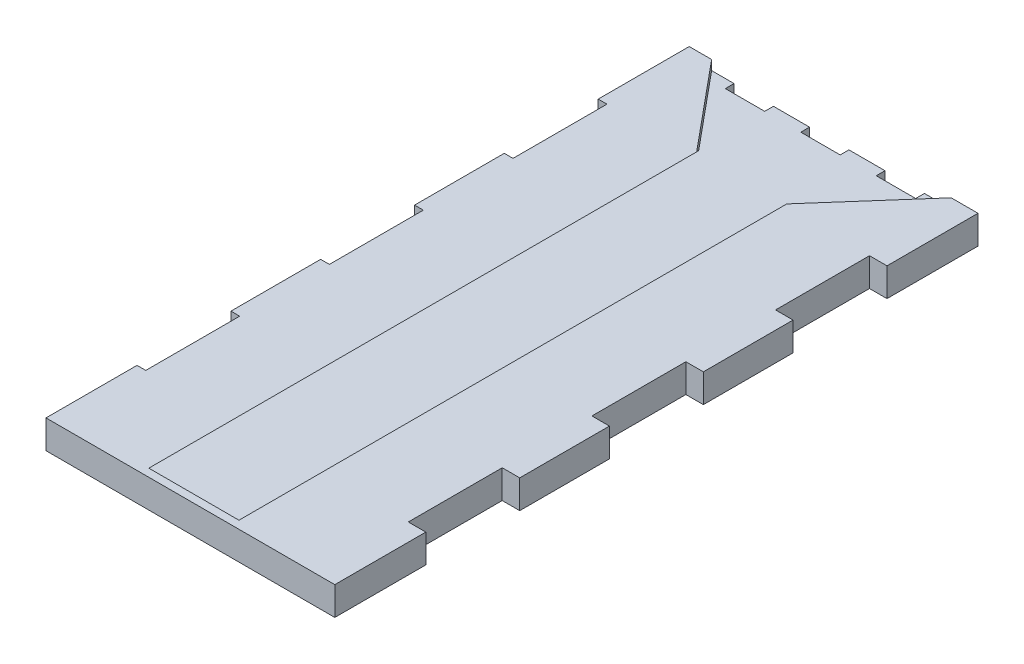
SolidWorks part; units mm, degrees
ref_plane "前视基准面" through (0, 0, 0) normal (0, 0, 1) x (1, 0, 0)
ref_plane "上视基准面" through (0, 0, 0) normal (0, 1, 0) x (1, 0, 0)
ref_plane "右视基准面" through (0, 0, 0) normal (1, 0, 0) x (0, 0, -1)
other "Configuration Table"
sketch "草图4" plane through (0, 0, 0) normal (0, 1, 0) x (1, 0, 0)
  line L6 (-30, -72.5) -> (30, -72.5)
  line L11 (-30, -72.5) -> (-30, 72.5)
  line L12 (-30, 72.5) -> (30, 72.5)
  line L13 (30, -72.5) -> (30, 72.5)
  line L14 (-30, -72.5) -> (30, 72.5) construction
  line L15 (-30, 72.5) -> (30, -72.5) construction
  point P0 (0, 0)
  dimension "D1" = 60
  dimension "D2" = 145
extrude "凸台-拉伸1" add sketch "草图4" along normal blind 6.5
sketch "草图5" plane through (0, 0, -72.5) normal (0, 0, -1) x (-1, 0, 0)
  line L0 (-30, 6.5) -> (30, 6.5) construction
  line L1 (30, 0) -> (21.75, 0)
  line L2 (30, 0) -> (30, 6.5)
  line L3 (30, 6.5) -> (21.75, 6.5)
  line L4 (21.75, 0) -> (21.75, 6.5)
  line L5 (-30, 0) -> (30, 0) construction
  line L6 (12.75, 0) -> (4.5, 0)
  line L7 (12.75, 0) -> (12.75, 6.5)
  line L8 (12.75, 6.5) -> (4.5, 6.5)
  line L9 (4.5, 0) -> (4.5, 6.5)
  line L10 (21.75, 0) -> (12.75, 0)
  line L11 (-4.5, 0) -> (-12.75, 0)
  line L12 (-4.5, 0) -> (-4.5, 6.5)
  line L13 (-4.5, 6.5) -> (-12.75, 6.5)
  line L14 (-12.75, 0) -> (-12.75, 6.5)
  line L15 (-21.75, 0) -> (-30, 0)
  line L16 (-21.75, 0) -> (-21.75, 6.5)
  line L17 (-21.75, 6.5) -> (-30, 6.5)
  line L18 (-30, 0) -> (-30, 6.5)
  line L19 (4.5, 0) -> (-4.5, 0)
  line L20 (-12.75, 0) -> (-21.75, 0)
  line M17 (-30, 0) -> (30, 0)
  line M18 (30, 0) -> (30, 6.5)
  line M19 (30, 6.5) -> (-30, 6.5)
  line M20 (-30, 6.5) -> (-30, 0)
  dimension "D1" = 9
extrude "凸台-拉伸2" add sketch "草图5" along normal blind 2 contours L16 M17 M19 M20 | L14 L12 M17 M19 | L9 L7 M17 M19 | L4 M17 M18 M19 region at (-25.875, 3.25, -72.5) region at (-8.625, 3.25, -72.5) region at (8.625, 3.25, -72.5) region at (25.875, 3.25, -72.5)
sketch "草图7" plane through (30, 0, 0) normal (1, 0, 0) x (0, 0, -1)
  line L0 (-72.5, 6.5) -> (74.5, 6.5) construction
  line L1 (-72.5, 0) -> (-51.7, 0)
  line L2 (-72.5, 0) -> (-72.5, 6.5)
  line L3 (-72.5, 6.5) -> (-51.7, 6.5)
  line L4 (-51.7, 0) -> (-51.7, 6.5)
  line L5 (-72.5, 0) -> (74.5, 0) construction
  line L6 (-30.2333, 0) -> (-9.7333, 0)
  line L7 (-30.2333, 0) -> (-30.2333, 6.5)
  line L8 (-30.2333, 6.5) -> (-9.7333, 6.5)
  line L9 (-9.7333, 0) -> (-9.7333, 6.5)
  line L10 (-51.7, 3.25) -> (-30.2333, 3.25) construction
  line L11 (11.7333, 0) -> (32.2333, 0)
  line L12 (11.7333, 0) -> (11.7333, 6.5)
  line L13 (11.7333, 6.5) -> (32.2333, 6.5)
  line L14 (32.2333, 0) -> (32.2333, 6.5)
  line L15 (53.7, 0) -> (74.5, 0)
  line L16 (53.7, 0) -> (53.7, 6.5)
  line L17 (53.7, 6.5) -> (74.5, 6.5)
  line L18 (74.5, 0) -> (74.5, 6.5)
  line L19 (-9.7333, 3.25) -> (11.7333, 3.25) construction
  line L20 (32.2333, 3.25) -> (53.7, 3.25) construction
  dimension "D1" = 20.8
  dimension "D2" = 20.5
extrude "凸台-拉伸3" add sketch "草图7" along normal blind 4
extrude "凸台-拉伸4" add sketch "草图7<2>" against normal blind 2 from surface starting at face at (-30, 3.25, -1)
sketch "草图7<2>" plane through (30, 0, 0) normal (1, 0, 0) x (0, 0, -1) same geometry as "草图7"
sketch "草图8" plane through (0, 0, 72.5) normal (0, 0, 1) x (1, 0, 0)
  line L0 (-10.3, 6.5) -> (-12.5, 4.3)
  line L1 (-32, 6.5) -> (34, 6.5) construction
  line L3 (12.5, 4.3) -> (10.3, 6.5)
  line L7 (-10.3, 6.5) -> (-10.3, 4.3) construction
  line L8 (-10.3, 6.5) -> (10.3, 6.5)
  line L9 (0, 0) -> (0, 6.5) construction
  line L10 (-12.5, 4.3) -> (-10.3, 4.3)
  line L11 (-10.3, 4.3) -> (10.3, 4.3)
  line L12 (10.3, 4.3) -> (12.5, 4.3)
  line L13 (10.3, 6.5) -> (-10.3, 6.5)
  line L14 (10.3, 6.5) -> (10.3, 4.3) construction
  line M13 (34, 6.5) -> (-32, 6.5)
  dimension "D1" = 2.2
  dimension "D2" = 20.6
extrude "切除-拉伸1" cut sketch "草图8" against normal through all from offset 1.8 contours L11 L12 L3 L0 L10 M13 region at (0, 5.3646, 72.5) offset against normal yes
sketch "草图9" plane through (0, 4.3, 0) normal (0, 1, 0) x (1, 0, 0)
  line L0 (-26.875, 74.5) -> (-10.3, 54.5)
  line L1 (-10.3, 54.5) -> (10.3, 54.5)
  line L2 (10.3, 74.5) -> (10.3, -70.7) construction
  line L3 (10.3, 54.5) -> (27.875, 74.5)
  line L4 (21.75, 74.5) -> (34, 74.5) construction
  line L5 (27.875, 74.5) -> (-26.875, 74.5)
  line L6 (-32, 74.5) -> (-21.75, 74.5) construction
  line L7 (-10.3, 74.5) -> (-10.3, -70.7) construction
  dimension "D1" = 20
extrude "切除-拉伸2" cut sketch "草图9" along normal through all
